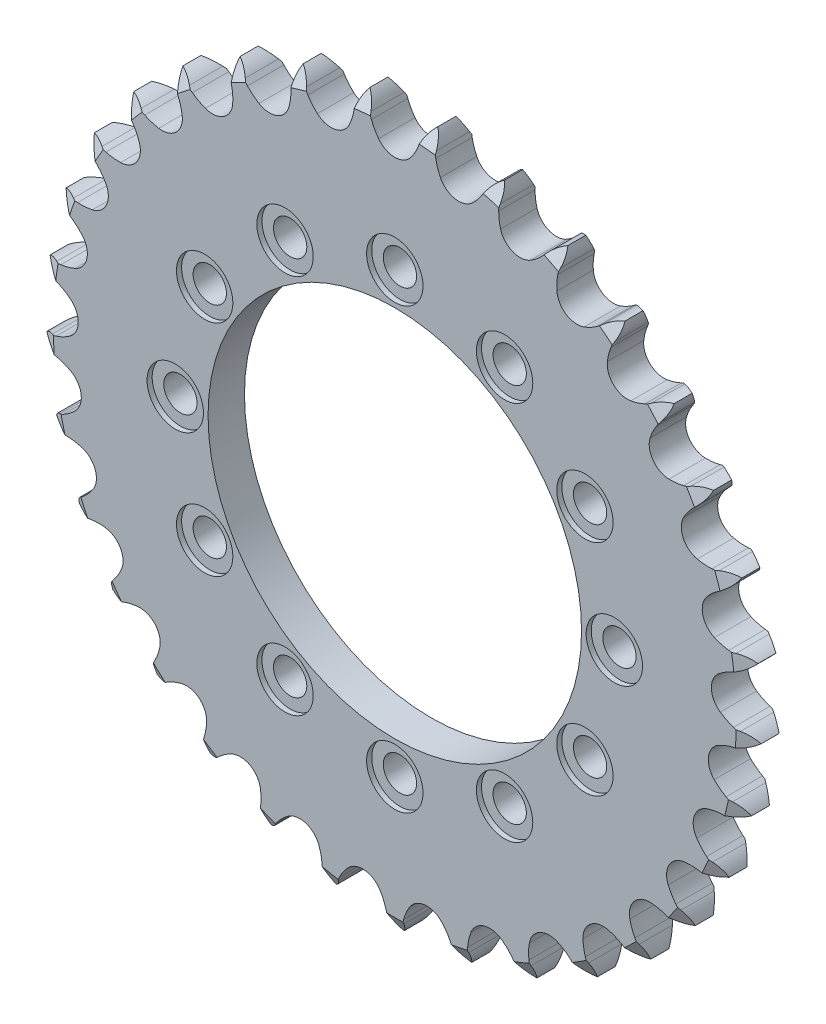
SolidWorks part; units mm, degrees
material "7075-T6 (SN)"
ref_plane "Front Plane" through (0, 0, 0) normal (0, 0, 1) x (1, 0, 0)
ref_plane "Top Plane" through (0, 0, 0) normal (0, 1, 0) x (1, 0, 0)
ref_plane "Right Plane" through (0, 0, 0) normal (1, 0, 0) x (0, 0, -1)
sketch "Work Sketch" plane through (0, 0, 0) normal (0, 0, 1) x (1, 0, 0)
  line L0 (0, 0) -> (0, 160.4542) construction
  line L1 (-112.0919, 66.8027) -> (87.2579, 66.8027) construction
  line L2 (5.0834, 120.8822) -> (5.0834, 112.9699) construction
  line L3 (-12.8497, 70.6081) -> (16.7256, 70.6081) construction
  line L4 (5.0834, 70.6081) -> (-6.0658, 62.2619) construction
  line L5 (5.0834, 70.6081) -> (-4.6352, 66.9715) construction
  line L6 (-4.6352, 66.9715) -> (-6.998, 73.2861)
  line L7 (-11.5114, 65.7464) -> (-7.1525, 65.7464) construction
  line L8 (-11.0622, 124.7602) -> (-11.0622, 110.2345) construction
  line L9 (0, 0) -> (-4.0639, 42.5596) construction
  circle A0 centre (0, 0) radius 66.8027
  circle A1 centre (0, 66.8027) radius 4.0088
  arc A2 (-4.6352, 66.9715) -> (-3.2092, 64.4003) centre (5.0609, 70.6677) ccw
  circle A3 centre (-11.0622, 65.7464) radius 6.4488
  point P23 (-3.2092, 64.4003)
  dimension "D1" = 133.6054
  dimension "D8" = 10.3767
  dimension "D2" = 8.0177
  dimension "D3" = 5.0834
  dimension "D4" = 3.8054
  dimension "D5" = 36.818
  dimension "D6" = 16.303
  dimension "D7" = 10.3767
  dimension "D9" = 1.0563
  dimension "D10" = 11.0622
  dimension "D11" = 5.455
sketch "Teeth Sketch" plane through (0, 0, 0) normal (0, 0, 1) x (1, 0, 0)
  line L0 (5.0224, 68.0064) -> (4.6352, 66.9715)
  line L1 (-8.8439, 92.6176) -> (-5.6513, 59.1829) construction
  line L2 (0, 0) -> (-12.8498, 132.1321) construction
  line L3 (7.9387, 67.7279) -> (8.123, 66.6385)
  line L4 (19011.2087, -199094.3845) -> (-19015.2726, 199136.9441) construction
  line L5 (0, 146.3285) -> (0, 56.9858) construction
  line L6 (17.8019, 65.8269) -> (17.2258, 64.8841)
  line L7 (0, -200000) -> (0, 200160.4542) construction
  line L8 (20.6128, 65.0016) -> (20.5877, 63.897)
  line L9 (-4.6352, 66.9715) -> (-6.998, 73.2861) construction
  line L10 (43.2949, 52.6844) -> (42.861, 51.6682)
  line L11 (-5.0224, 68.0064) -> (-4.6352, 66.9715)
  line L12 (29.938, 61.2683) -> (29.1939, 60.4515)
  line L13 (32.5419, 59.9259) -> (32.3082, 58.846)
  line L14 (40.9921, 54.4953) -> (40.1069, 53.8341)
  line L15 (50.5647, 45.7527) -> (49.5703, 45.271)
  line L16 (52.4831, 43.5387) -> (51.8648, 42.623)
  line L17 (58.3096, 35.3565) -> (57.2421, 35.0716)
  line L18 (59.7744, 32.8194) -> (58.9939, 32.0373)
  line L19 (63.9472, 23.6824) -> (62.845, 23.6047)
  line L20 (64.9053, 20.9139) -> (63.9909, 20.2936)
  line L21 (67.2735, 11.1523) -> (66.1765, 11.2846)
  line L22 (67.6904, 8.2526) -> (66.6751, 7.8165)
  line L23 (68.1683, -1.7808) -> (67.1162, -1.4433)
  line L24 (68.0289, -4.7071) -> (66.9495, -4.9431)
  line L25 (66.5994, -14.6496) -> (65.6302, -14.119)
  line L26 (65.9088, -17.4966) -> (64.8042, -17.524)
  line L27 (62.6234, -26.9889) -> (61.7722, -26.2845)
  line L28 (61.4065, -29.6537) -> (60.3166, -29.4716)
  line L29 (56.3841, -38.3527) -> (55.6815, -37.4999)
  line L30 (54.6848, -40.739) -> (53.6491, -40.354)
  line L31 (48.1068, -48.3304) -> (47.5783, -47.3601)
  line L32 (45.9866, -50.352) -> (45.0425, -49.7779)
  line L33 (38.0909, -56.5613) -> (37.7556, -55.5085)
  line L34 (35.6264, -58.1451) -> (34.808, -57.4027)
  line L35 (26.6983, -62.7479) -> (26.5682, -61.6506)
  line L36 (23.9786, -63.8367) -> (23.3155, -62.9529)
  line L37 (14.3407, -66.6666) -> (14.4207, -65.5646)
  line L38 (11.4641, -67.221) -> (10.9802, -66.2277)
  line L39 (1.4648, -68.1759) -> (1.7519, -67.1089)
  line L40 (-1.4648, -68.1759) -> (-1.7519, -67.1089)
  line L41 (-11.4641, -67.221) -> (-10.9802, -66.2277)
  line L42 (-14.3407, -66.6666) -> (-14.4207, -65.5646)
  line L43 (-23.9786, -63.8367) -> (-23.3155, -62.9529)
  line L44 (-26.6983, -62.7479) -> (-26.5682, -61.6506)
  line L45 (-35.6264, -58.1451) -> (-34.808, -57.4027)
  line L46 (-38.0909, -56.5613) -> (-37.7556, -55.5085)
  line L47 (-45.9866, -50.352) -> (-45.0425, -49.7779)
  line L48 (-48.1068, -48.3304) -> (-47.5783, -47.3601)
  line L49 (-54.6848, -40.739) -> (-53.6491, -40.354)
  line L50 (-56.3841, -38.3527) -> (-55.6815, -37.4999)
  line L51 (-61.4065, -29.6537) -> (-60.3166, -29.4716)
  line L52 (-62.6234, -26.9889) -> (-61.7722, -26.2845)
  line L53 (-65.9088, -17.4966) -> (-64.8042, -17.524)
  line L54 (-66.5994, -14.6496) -> (-65.6302, -14.119)
  line L55 (-68.0289, -4.7071) -> (-66.9495, -4.9431)
  line L56 (-68.1683, -1.7808) -> (-67.1162, -1.4433)
  line L57 (-67.6904, 8.2526) -> (-66.6751, 7.8165)
  line L58 (-67.2735, 11.1523) -> (-66.1765, 11.2846)
  line L59 (-64.9053, 20.9139) -> (-63.9909, 20.2936)
  line L60 (-63.9472, 23.6824) -> (-62.845, 23.6047)
  line L61 (-59.7744, 32.8194) -> (-58.9939, 32.0373)
  line L62 (-58.3096, 35.3565) -> (-57.2421, 35.0716)
  line L63 (-52.4831, 43.5387) -> (-51.8648, 42.623)
  line L64 (-50.5647, 45.7527) -> (-49.5703, 45.271)
  line L65 (-43.2949, 52.6844) -> (-42.861, 51.6682)
  line L66 (-40.9921, 54.4953) -> (-40.1069, 53.8341)
  line L67 (-32.5419, 59.9259) -> (-32.3082, 58.846)
  line L68 (-29.938, 61.2683) -> (-29.1939, 60.4515)
  line L69 (-20.6128, 65.0016) -> (-20.5877, 63.897)
  line L70 (-17.8019, 65.8269) -> (-17.2258, 64.8841)
  line L71 (-7.9387, 67.7279) -> (-8.123, 66.6385)
  arc A0 (-6.8704, 70.647) -> (-5.0224, 68.0064) centre (-11.0622, 65.7464) cw
  circle A1 centre (-11.0622, 65.7464) radius 6.4488 construction
  arc A2 (-3.2092, 64.4003) -> (-4.6352, 66.9715) centre (5.0609, 70.6677) cw
  arc A3 (-4.6352, 66.9715) -> (-3.2092, 64.4003) centre (5.0609, 70.6677) ccw construction
  circle A4 centre (0, 66.8027) radius 4.0088 construction
  arc A5 (-3.2092, 64.4003) -> (3.2092, 64.4003) centre (0, 66.8027) ccw
  arc A6 (3.2092, 64.4003) -> (4.6352, 66.9715) centre (-5.0609, 70.6677) ccw
  arc A7 (6.8704, 70.647) -> (5.0224, 68.0064) centre (11.0622, 65.7464) ccw
  arc A8 (6.6238, 70.6705) -> (7.9387, 67.7279) centre (1.5803, 66.6518) cw
  arc A9 (9.0366, 63.8438) -> (8.123, 66.6385) centre (18.3434, 68.4328) cw
  arc A10 (9.0366, 63.8438) -> (15.3391, 62.6291) centre (12.6425, 65.5955) ccw
  arc A11 (15.3391, 62.6291) -> (17.2258, 64.8841) centre (8.4044, 70.3484) ccw
  arc A12 (20.1163, 68.0701) -> (17.8019, 65.8269) centre (23.3049, 62.4647) ccw
  arc A13 (19.8786, 68.1399) -> (20.6128, 65.0016) centre (14.1657, 65.1482) cw
  arc A14 (20.9558, 60.9799) -> (20.5877, 63.897) centre (30.9629, 63.7246) cw
  arc A15 (20.9558, 60.9799) -> (26.9145, 58.5944) centre (24.8281, 62.0175) ccw
  arc A16 (26.9145, 58.5944) -> (29.1939, 60.4515) centre (21.5661, 67.4865) ccw
  arc A17 (32.6351, 63.0329) -> (29.938, 61.2683) centre (34.7052, 56.9254) ccw
  arc A18 (32.4149, 63.1465) -> (32.5419, 59.9259) centre (26.2391, 61.29) cw
  arc A19 (32.1176, 55.912) -> (32.3082, 58.846) centre (42.4634, 56.7133) cw
  arc A20 (32.1176, 55.912) -> (37.5172, 52.4419) centre (36.1163, 56.198) ccw
  arc A21 (37.5172, 52.4419) -> (40.1069, 53.8341) centre (33.9483, 62.1856) ccw
  arc A22 (43.9744, 55.7176) -> (40.9921, 54.4953) centre (44.8513, 49.3287) ccw
  arc A23 (43.7796, 55.8708) -> (43.2949, 52.6844) centre (37.3641, 55.2167) cw
  arc A24 (42.1187, 48.8233) -> (42.861, 51.6682) centre (52.429, 47.6521) cw
  arc A25 (42.1187, 48.8233) -> (46.7639, 44.3941) centre (46.0991, 48.3474) ccw
  arc A26 (46.7639, 44.3941) -> (49.5703, 45.271) centre (45.1035, 54.637) ccw
  arc A27 (53.7244, 46.3885) -> (50.5647, 45.7527) centre (53.3763, 39.9491) ccw
  arc A28 (53.5621, 46.5757) -> (52.4831, 43.5387) centre (47.1387, 47.1476) cw
  arc A29 (50.5974, 39.97) -> (51.8648, 42.623) centre (60.4998, 36.8687) cw
  arc A30 (50.5974, 39.97) -> (54.3205, 34.7417) centre (54.4159, 38.7494) ccw
  arc A31 (54.3205, 34.7417) -> (57.2421, 35.0716) centre (54.6285, 45.1138) ccw
  arc A32 (61.5326, 35.3828) -> (58.3096, 35.3565) centre (59.9721, 29.1257) ccw
  arc A33 (61.4087, 35.5974) -> (59.7744, 32.8194) centre (55.2096, 37.3746) cw
  arc A34 (57.2474, 29.6721) -> (58.9939, 32.0373) centre (66.384, 24.7528) cw
  arc A35 (57.2474, 29.6721) -> (59.9137, 23.8336) centre (60.7659, 27.7508) ccw
  arc A36 (59.9137, 23.8336) -> (62.845, 23.6047) centre (62.1792, 33.96) ccw
  arc A37 (67.1168, 23.0983) -> (63.9472, 23.6824) centre (64.4004, 17.2495) ccw
  arc A38 (67.0358, 23.3324) -> (64.9053, 20.9139) centre (61.2851, 26.2507) cw
  arc A39 (61.8283, 18.3017) -> (63.9909, 20.2936) centre (69.8688, 11.7422) cw
  arc A40 (61.8283, 18.3017) -> (63.3416, 12.0642) centre (64.9196, 15.7493) ccw
  arc A41 (63.3416, 12.0642) -> (66.1765, 11.2846) centre (67.4825, 21.5788) ccw
  arc A42 (70.2753, 9.9789) -> (67.2735, 11.1523) centre (66.5011, 4.7499) ccw
  arc A43 (70.2401, 10.2242) -> (67.6904, 8.2526) centre (65.1456, 14.178) cw
  arc A44 (64.1746, 6.2699) -> (66.6751, 7.8165) centre (70.8284, -1.6927) cw
  arc A45 (64.1746, 6.2699) -> (64.48, -0.1413) centre (66.727, 3.1786) ccw
  arc A46 (64.48, -0.1413) -> (67.1162, -1.4433) centre (70.3468, 8.4177) ccw
  arc A47 (70.8939, -3.5011) -> (68.1683, -1.7808) centre (66.1983, -7.9213) ccw
  arc A48 (70.9057, -3.2536) -> (68.0289, -4.7071) centre (66.6515, 1.5929) cw
  arc A49 (64.2015, -5.9885) -> (66.9495, -4.9431) centre (69.2281, -15.0665) cw
  arc A50 (64.2015, -5.9885) -> (63.2881, -12.3417) centre (66.1227, -9.507) ccw
  arc A51 (63.2881, -12.3417) -> (65.6302, -14.119) centre (70.6686, -5.0476) ccw
  arc A52 (68.9501, -16.8546) -> (66.5994, -14.6496) centre (63.5029, -20.3063) ccw
  arc A53 (69.0085, -16.6138) -> (65.9088, -17.4966) centre (65.7485, -11.0498) cw
  arc A54 (61.908, -18.0305) -> (64.8042, -17.524) centre (65.1257, -27.8957) cw
  arc A55 (61.908, -18.0305) -> (59.8087, -24.096) centre (63.1286, -21.849) ccw
  arc A56 (59.8087, -24.096) -> (61.7722, -26.2845) centre (68.4363, -18.3305) ccw
  arc A57 (64.5144, -29.5989) -> (62.6234, -26.9889) centre (58.5123, -31.9573) ccw
  arc A58 (64.6173, -29.3735) -> (61.4065, -29.6537) centre (62.4691, -23.2931) cw
  arc A59 (57.3769, -29.4209) -> (60.3166, -29.4716) centre (58.6695, -39.7167) cw
  arc A60 (57.3769, -29.4209) -> (54.1677, -34.9794) centre (57.8528, -33.4013) ccw
  arc A61 (54.1677, -34.9794) -> (55.6815, -37.4999) centre (63.7305, -30.9509) ccw
  arc A62 (57.7469, -41.2734) -> (56.3841, -38.3527) centre (51.4069, -42.4533) ccw
  arc A63 (57.8906, -41.0716) -> (54.6848, -40.739) centre (56.932, -34.6945) cw
  arc A64 (50.7721, -39.7478) -> (53.6491, -40.354) centre (50.0928, -50.1023) cw
  arc A65 (50.7721, -39.7478) -> (46.5689, -44.5986) centre (50.4861, -43.7465) ccw
  arc A66 (46.5689, -44.5986) -> (47.5783, -47.3601) centre (56.7213, -42.4527) ccw
  arc A67 (48.8923, -51.4562) -> (48.1068, -48.3304) centre (42.4436, -51.415) ccw
  arc A68 (49.0716, -51.2853) -> (45.9866, -50.352) centre (49.3372, -44.842) cw
  arc A69 (42.3322, -48.6382) -> (45.0425, -49.7779) centre (39.7057, -58.677) cw
  arc A70 (42.3322, -48.6382) -> (37.287, -52.6059) centre (41.2947, -52.5105) ccw
  arc A71 (37.287, -52.6059) -> (37.7556, -55.5085) centre (47.662, -52.4201) ccw
  arc A72 (38.2706, -59.7793) -> (38.0909, -56.5613) centre (31.9463, -58.5183) ccw
  arc A73 (38.479, -59.6453) -> (35.6264, -58.1451) centre (39.9592, -53.3687) cw
  arc A74 (32.3624, -55.7707) -> (34.808, -57.4027) centre (27.8834, -65.131) cw
  arc A75 (32.3624, -55.7707) -> (26.6574, -58.7118) centre (30.6108, -59.3766) ccw
  arc A76 (26.6574, -58.7118) -> (26.5682, -61.6506) centre (36.8801, -60.4929) ccw
  arc A77 (26.2657, -65.9417) -> (26.6983, -62.7479) centre (20.2943, -63.5067) ccw
  arc A78 (26.4957, -65.8497) -> (23.9786, -63.8367) centre (29.137, -59.9666) cw
  arc A79 (21.2229, -60.8875) -> (23.3155, -62.9529) centre (15.0534, -69.2309) cw
  arc A80 (21.2229, -60.8875) -> (15.0644, -62.6958) centre (18.8205, -64.0967) ccw
  arc A81 (15.0644, -62.6958) -> (14.4207, -65.5646) centre (24.7653, -66.3793) ccw
  arc A82 (13.3114, -69.7209) -> (14.3407, -66.6666) centre (7.9088, -66.1998) ccw
  arc A83 (13.5547, -69.674) -> (11.4641, -67.221) centre (17.2617, -64.3972) cw
  arc A84 (9.3163, -63.8036) -> (10.9802, -66.2277) centre (1.6794, -70.8287) cw
  arc A85 (9.3163, -63.8036) -> (2.9269, -64.4137) centre (6.35, -66.5002) ccw
  arc A86 (2.9269, -64.4137) -> (1.7519, -67.1089) centre (11.7554, -69.8666) ccw
  arc A87 (-0.1239, -70.9802) -> (1.4648, -68.1759) centre (-4.7625, -66.5002) ccw
  arc A88 (0.1239, -70.9802) -> (-1.4648, -68.1759) centre (4.7625, -66.5002) cw
  arc A89 (-2.9269, -64.4137) -> (-1.7519, -67.1089) centre (-11.7554, -69.8666) cw
  arc A90 (-2.9269, -64.4137) -> (-9.3163, -63.8036) centre (-6.35, -66.5002) ccw
  arc A91 (-9.3163, -63.8036) -> (-10.9802, -66.2277) centre (-1.6794, -70.8287) ccw
  arc A92 (-13.5547, -69.674) -> (-11.4641, -67.221) centre (-17.2617, -64.3972) ccw
  arc A93 (-13.3114, -69.7209) -> (-14.3407, -66.6666) centre (-7.9088, -66.1998) cw
  arc A94 (-15.0644, -62.6958) -> (-14.4207, -65.5646) centre (-24.7653, -66.3793) cw
  arc A95 (-15.0644, -62.6958) -> (-21.2229, -60.8875) centre (-18.8205, -64.0967) ccw
  arc A96 (-21.2229, -60.8875) -> (-23.3155, -62.9529) centre (-15.0534, -69.2309) ccw
  arc A97 (-26.4957, -65.8497) -> (-23.9786, -63.8367) centre (-29.137, -59.9666) ccw
  arc A98 (-26.2657, -65.9417) -> (-26.6983, -62.7479) centre (-20.2943, -63.5067) cw
  arc A99 (-26.6574, -58.7118) -> (-26.5682, -61.6506) centre (-36.8801, -60.4929) cw
  arc A100 (-26.6574, -58.7118) -> (-32.3624, -55.7707) centre (-30.6108, -59.3766) ccw
  arc A101 (-32.3624, -55.7707) -> (-34.808, -57.4027) centre (-27.8834, -65.131) ccw
  arc A102 (-38.479, -59.6453) -> (-35.6264, -58.1451) centre (-39.9592, -53.3687) ccw
  arc A103 (-38.2706, -59.7793) -> (-38.0909, -56.5613) centre (-31.9463, -58.5183) cw
  arc A104 (-37.287, -52.6059) -> (-37.7556, -55.5085) centre (-47.662, -52.4201) cw
  arc A105 (-37.287, -52.6059) -> (-42.3322, -48.6382) centre (-41.2947, -52.5105) ccw
  arc A106 (-42.3322, -48.6382) -> (-45.0425, -49.7779) centre (-39.7057, -58.677) ccw
  arc A107 (-49.0716, -51.2853) -> (-45.9866, -50.352) centre (-49.3372, -44.842) ccw
  arc A108 (-48.8923, -51.4562) -> (-48.1068, -48.3304) centre (-42.4436, -51.415) cw
  arc A109 (-46.5689, -44.5986) -> (-47.5783, -47.3601) centre (-56.7213, -42.4527) cw
  arc A110 (-46.5689, -44.5986) -> (-50.7721, -39.7478) centre (-50.4861, -43.7465) ccw
  arc A111 (-50.7721, -39.7478) -> (-53.6491, -40.354) centre (-50.0928, -50.1023) ccw
  arc A112 (-57.8906, -41.0716) -> (-54.6848, -40.739) centre (-56.932, -34.6945) ccw
  arc A113 (-57.7469, -41.2734) -> (-56.3841, -38.3527) centre (-51.4069, -42.4533) cw
  arc A114 (-54.1677, -34.9794) -> (-55.6815, -37.4999) centre (-63.7305, -30.9509) cw
  arc A115 (-54.1677, -34.9794) -> (-57.3769, -29.4209) centre (-57.8528, -33.4013) ccw
  arc A116 (-57.3769, -29.4209) -> (-60.3166, -29.4716) centre (-58.6695, -39.7167) ccw
  arc A117 (-64.6173, -29.3735) -> (-61.4065, -29.6537) centre (-62.4691, -23.2931) ccw
  arc A118 (-64.5144, -29.5989) -> (-62.6234, -26.9889) centre (-58.5123, -31.9573) cw
  arc A119 (-59.8087, -24.096) -> (-61.7722, -26.2845) centre (-68.4363, -18.3305) cw
  arc A120 (-59.8087, -24.096) -> (-61.908, -18.0305) centre (-63.1286, -21.849) ccw
  arc A121 (-61.908, -18.0305) -> (-64.8042, -17.524) centre (-65.1257, -27.8957) ccw
  arc A122 (-69.0085, -16.6138) -> (-65.9088, -17.4966) centre (-65.7485, -11.0498) ccw
  arc A123 (-68.9501, -16.8546) -> (-66.5994, -14.6496) centre (-63.5029, -20.3063) cw
  arc A124 (-63.2881, -12.3417) -> (-65.6302, -14.119) centre (-70.6686, -5.0476) cw
  arc A125 (-63.2881, -12.3417) -> (-64.2015, -5.9885) centre (-66.1227, -9.507) ccw
  arc A126 (-64.2015, -5.9885) -> (-66.9495, -4.9431) centre (-69.2281, -15.0665) ccw
  arc A127 (-70.9057, -3.2536) -> (-68.0289, -4.7071) centre (-66.6515, 1.5929) ccw
  arc A128 (-70.8939, -3.5011) -> (-68.1683, -1.7808) centre (-66.1983, -7.9213) cw
  arc A129 (-64.48, -0.1413) -> (-67.1162, -1.4433) centre (-70.3468, 8.4177) cw
  arc A130 (-64.48, -0.1413) -> (-64.1746, 6.2699) centre (-66.727, 3.1786) ccw
  arc A131 (-64.1746, 6.2699) -> (-66.6751, 7.8165) centre (-70.8284, -1.6927) ccw
  arc A132 (-70.2401, 10.2242) -> (-67.6904, 8.2526) centre (-65.1456, 14.178) ccw
  arc A133 (-70.2753, 9.9789) -> (-67.2735, 11.1523) centre (-66.5011, 4.7499) cw
  arc A134 (-63.3416, 12.0642) -> (-66.1765, 11.2846) centre (-67.4825, 21.5788) cw
  arc A135 (-63.3416, 12.0642) -> (-61.8283, 18.3017) centre (-64.9196, 15.7493) ccw
  arc A136 (-61.8283, 18.3017) -> (-63.9909, 20.2936) centre (-69.8688, 11.7422) ccw
  arc A137 (-67.0358, 23.3324) -> (-64.9053, 20.9139) centre (-61.2851, 26.2507) ccw
  arc A138 (-67.1168, 23.0983) -> (-63.9472, 23.6824) centre (-64.4004, 17.2495) cw
  arc A139 (-59.9137, 23.8336) -> (-62.845, 23.6047) centre (-62.1792, 33.96) cw
  arc A140 (-59.9137, 23.8336) -> (-57.2474, 29.6721) centre (-60.7659, 27.7508) ccw
  arc A141 (-57.2474, 29.6721) -> (-58.9939, 32.0373) centre (-66.384, 24.7528) ccw
  arc A142 (-61.4087, 35.5974) -> (-59.7744, 32.8194) centre (-55.2096, 37.3746) ccw
  arc A143 (-61.5326, 35.3828) -> (-58.3096, 35.3565) centre (-59.9721, 29.1257) cw
  arc A144 (-54.3205, 34.7417) -> (-57.2421, 35.0716) centre (-54.6285, 45.1138) cw
  arc A145 (-54.3205, 34.7417) -> (-50.5974, 39.97) centre (-54.4159, 38.7494) ccw
  arc A146 (-50.5974, 39.97) -> (-51.8648, 42.623) centre (-60.4998, 36.8687) ccw
  arc A147 (-53.5621, 46.5757) -> (-52.4831, 43.5387) centre (-47.1387, 47.1476) ccw
  arc A148 (-53.7244, 46.3885) -> (-50.5647, 45.7527) centre (-53.3763, 39.9491) cw
  arc A149 (-46.7639, 44.3941) -> (-49.5703, 45.271) centre (-45.1035, 54.637) cw
  arc A150 (-46.7639, 44.3941) -> (-42.1187, 48.8233) centre (-46.0991, 48.3474) ccw
  arc A151 (-42.1187, 48.8233) -> (-42.861, 51.6682) centre (-52.429, 47.6521) ccw
  arc A152 (-43.7796, 55.8708) -> (-43.2949, 52.6844) centre (-37.3641, 55.2167) ccw
  arc A153 (-43.9744, 55.7176) -> (-40.9921, 54.4953) centre (-44.8513, 49.3287) cw
  arc A154 (-37.5172, 52.4419) -> (-40.1069, 53.8341) centre (-33.9483, 62.1856) cw
  arc A155 (-37.5172, 52.4419) -> (-32.1176, 55.912) centre (-36.1163, 56.198) ccw
  arc A156 (-32.1176, 55.912) -> (-32.3082, 58.846) centre (-42.4634, 56.7133) ccw
  arc A157 (-32.4149, 63.1465) -> (-32.5419, 59.9259) centre (-26.2391, 61.29) ccw
  arc A158 (-32.6351, 63.0329) -> (-29.938, 61.2683) centre (-34.7052, 56.9254) cw
  arc A159 (-26.9145, 58.5944) -> (-29.1939, 60.4515) centre (-21.5661, 67.4865) cw
  arc A160 (-26.9145, 58.5944) -> (-20.9558, 60.9799) centre (-24.8281, 62.0175) ccw
  arc A161 (-20.9558, 60.9799) -> (-20.5877, 63.897) centre (-30.9629, 63.7246) ccw
  arc A162 (-19.8786, 68.1399) -> (-20.6128, 65.0016) centre (-14.1657, 65.1482) ccw
  arc A163 (-20.1163, 68.0701) -> (-17.8019, 65.8269) centre (-23.3049, 62.4647) cw
  arc A164 (-15.3391, 62.6291) -> (-17.2258, 64.8841) centre (-8.4044, 70.3484) cw
  arc A165 (-15.3391, 62.6291) -> (-9.0366, 63.8438) centre (-12.6425, 65.5955) ccw
  arc A166 (-9.0366, 63.8438) -> (-8.123, 66.6385) centre (-18.3434, 68.4328) ccw
  arc A167 (-6.6238, 70.6705) -> (-7.9387, 67.7279) centre (-1.5803, 66.6518) ccw
  point P77 (0, 0)
  dimension "D1" = 5.455
  dimension "D2" = 5.555
  dimension "D3" = 33
extrude "Extrusion" add sketch "Teeth Sketch" along normal blind 7.2136 contours A0 region at (0, 0, 0)
ref_axis "Axis2" through (0, 0, 38.9715) along (0, 0, -1)
hole_wizard "M6 Clearance Hole1" positions "Sketch6" profile "Sketch7" hole size "M6" standard "ANSI Metric"
sketch "Sketch6" plane through (0, 0, 0) normal (0, 0, -1) x (-1, 0, 0)
  circle A0 centre (0, 0) radius 43.5
  point P0 (0, 43.5)
  dimension "D1" = 87
sketch "Sketch7" plane through (0, 43.5, 0) normal (1, 0, 0) x (0, 1, 0)
  line L0 (0, 0) -> (0, 19.2548)
  line L1 (0, 19.2548) -> (3.3, 17.272)
  line L2 (3.3, 17.272) -> (3.3, 0)
  line L5 (3.3, 0) -> (0, 0)
  line L10 (0, 19.2548) -> (-3.3, 17.272) construction
  line L11 (0, -6.35) -> (0, 107.95) construction
  dimension "Hole Dia." = 6.6
  dimension "Hole Depth" = 17.272
  dimension "Drill Angle" = 118
pattern_circular "CirPattern1" count 12 over 360 about axis through (0, 0, 38.9715) along (0, 0, -1) of "M6 Clearance Hole1"
sketch "Sketch8" plane through (0, 0, 0) normal (0, 0, -1) x (-1, 0, 0)
  circle A0 centre (0, 0) radius 37
  dimension "D1" = 74
extrude "Cut-Extrude1" cut sketch "Sketch8" against normal through all both and the other way through all
ref_plane "Sprocket Center Plane" through (0, 0, 3.6068) normal (0, 0, 1) x (1, 0, 0)
sketch "Pitch Circle" plane through (0, 0, 3.6068) normal (0, 0, -1) x (-1, 0, 0)
  circle A0 centre (0, 0) radius 66.8027 construction
  dimension "D1" = 133.6054
ref_plane "Center Plane" through (0, 0, 3.6068) normal (0, 0, 1) x (1, 0, 0)
ref_axis "Axis1" through (0, 0, 7.2136) along (0, 0, -1)
sketch "Sketch5" plane through (0, 0, 0) normal (1, 0, 0) x (0, 0, -1)
  line L0 (-1.8288, -70.8482) -> (-5.3848, -70.8482)
  line L1 (-7.2136, -51.2753) -> (0, -51.2753) construction
  line L2 (-5.3848, -70.8482) -> (-5.3848, -67.6547)
  line L3 (-5.3848, -67.6547) -> (-7.2136, -67.6547)
  line L4 (-7.2136, -67.6547) -> (-5.3848, -70.8482)
  line L5 (-7.2136, -67.6547) -> (-7.2136, -70.8482)
  line L6 (-7.2136, -70.8482) -> (-5.3848, -70.8482)
  line L10 (-7.2136, -70.8482) -> (0, -70.8482) construction
  dimension "D1" = 3.556
  dimension "D2" = 3.1936
  dimension "D3" = 1.8288
revolve "Cut-Revolve1" cut sketch "Sketch5" angle 360 about axis through (0, 0, 7.2136) along (0, 0, -1) region at (0, -69.7837, 6.604)
mirror "Mirror1" about plane through (0, 0, 3.6068) normal (0, 0, 1) of "Cut-Revolve1"
sketch "Sketch10" plane through (0, 0, 0) normal (0, 0, 1) x (1, 0, 0)
  circle A0 centre (-43.5, 0) radius 5.588
  dimension "D1" = 11.176
extrude "Cut-Extrude2" cut sketch "Sketch10" against normal blind 1.016 from surface starting at face at (-37, 0, 7.2136)
pattern_circular "CirPattern2" count 12 over 360 about axis through (0, 0, 38.9715) along (0, 0, -1) of "Cut-Extrude2"
ref_plane "Half Plane" through (0, 0, 3.6068) normal (0, 0, 1) x (1, 0, 0)
sketch "Motor Shaft Sprocket Dimensions" plane through (0, 0, 3.6068) normal (0, 0, 1) x (1, 0, 0)
  line L0 (0, 0) -> (-177.8, 0)
  line L1 (-177.8, 0) -> (-177.8, 23.6982)
  line L2 (-180.2273, 51.0991) -> (-5.8945, 66.5421)
  line L3 (-187.3193, -2.1104) -> (-23.1174, -62.6753)
  line L4 (-5.8945, 66.5421) -> (0, 0)
  line L5 (0, 0) -> (-23.1174, -62.6753)
  circle A0 centre (-177.8, 23.6982) radius 27.5082
  circle A1 centre (0, 0) radius 66.8027 construction
  dimension "D3" = 55.0164
  dimension "D1" = 177.8
  dimension "D2" = 23.6982
  dimension "D4" = 205.308
equation "\"P\"= 0.500'//Chain Pitch"
equation "\"N\"= 33'//Number of Teeth"
equation "\"Dr\"= 5 / 16'//Roller Diameter"
equation "\"Ds\"= 1.0005 * \"Dr\" + 0.003'Seating Curve DIameter"
equation "\"R\"= \"Ds\" / 2"
equation "\"A\"= 35 + 60 / \"N\""
equation "\"B\"= 18 - 56 / \"N\""
equation "\"ac\"= 0.8 * \"Dr\""
equation "\"M\"= 0.8 * \"Dr\" * cos ( 35 + 60 / \"N\" )"
equation "\"T\"= 0.8 * \"Dr\" * sin ( 35 + 60 / \"N\" )"
equation "\"E\"= 1.3025 * \"Dr\" + 0.0015"
equation "\"Chordal Length of Arc xy\"= ( 2.605 * \"Dr\" + 0.003 ) * sin ( 9 - 28 / \"N\" )"
equation "\"yz\"= \"Dr\" * ( 1.4 * sin ( 17 - 64 / \"N\" ) - 0.8 * sin ( 18 - 56 / \"N\" ) )"
equation "\"ab\"= 1.4 * \"Dr\""
equation "\"W\"= 1.4 * \"Dr\" * cos ( 180 / \"N\" )"
equation "\"V\"= 1.4 * \"Dr\" * sin ( 180 / \"N\" )"
equation "\"F\"= \"Dr\" * ( 0.8 * cos ( 18 - 56 / \"N\" ) + 1.4 * cos ( 17 - 64 / \"N\" ) - 1.3025 )"
equation "\"H\"= sqr ( \"F\" ^ 2 - ( 1.4 * \"Dr\" - \"P\" / 2 ) ^ 2 )"
equation "\"S\"= \"P\" / 2 * cos ( 180 / \"N\" ) + \"H\" * sin ( 180 / \"N\" )"
equation "\"PD\"= \"P\" / ( sin ( 180 / \"N\" ) )"
equation "\"D1@Work Sketch\" = \"PD\""
equation "\"D3@Work Sketch\" = \"M\""
equation "\"D4@Work Sketch\" = \"T\""
equation "\"D5@Work Sketch\" = \"A\""
equation "\"D6@Work Sketch\" = \"B\""
equation "\"D7@Work Sketch\" = \"E\""
equation "\"D8@Work Sketch\" = \"E\""
equation "\"D9@Work Sketch\" = \"V\""
equation "\"D10@Work Sketch\" = \"W\""
equation "\"D2@Work Sketch\" = \"R\" * 2"
equation "\"D11@Work Sketch\" = 180 / \"N\""
equation "\"D2@Teeth Sketch\" = 180 / \"N\" + 0.1"
equation "\"D3@Teeth Sketch\" = \"N\""
equation "\"Edge Thickness\"=0.5"
equation "\"D1@Pitch Circle\"=\"PD\""
equation "\"ST\"= 0.284'//Sprocket Thickness"
